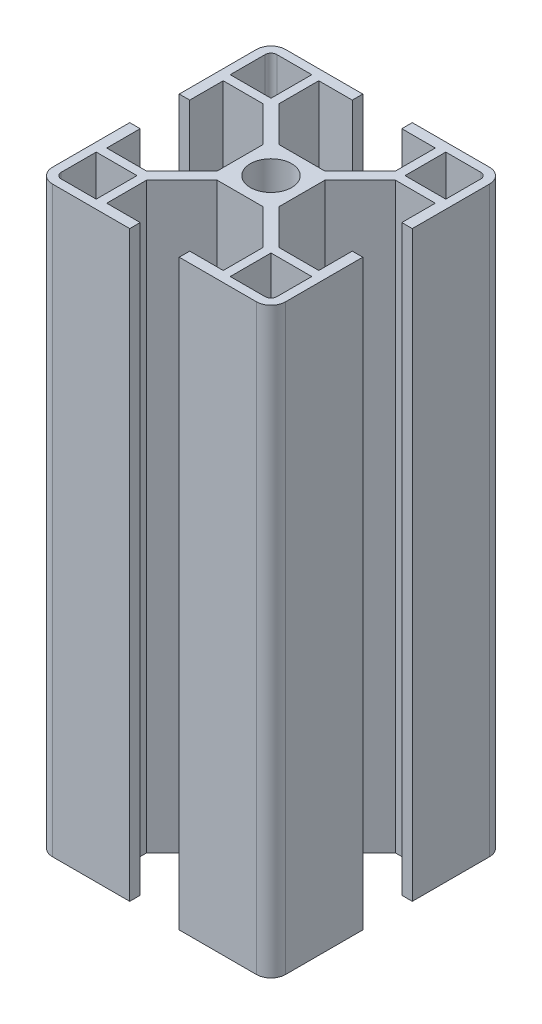
SolidWorks part; units mm, degrees
ref_plane "前视基准面" through (0, 0, 0) normal (0, 0, 1) x (1, 0, 0)
ref_plane "上视基准面" through (0, 0, 0) normal (0, 1, 0) x (1, 0, 0)
ref_plane "右视基准面" through (0, 0, 0) normal (1, 0, 0) x (0, 0, -1)
other "Configuration Table"
sketch "草图1" plane through (0, 0, 0) normal (0, 1, 0) x (1, 0, 0)
  line L0 (-28.4403, 0) -> (36.2792, 0) construction
  line L1 (0, 26.4889) -> (0, -19.5972) construction
  line L2 (0, 0) -> (-20.5491, 20.5491) construction
  line L3 (-20, 20) -> (-4.25, 20)
  line L4 (-4.25, 20) -> (-4.25, 18.2)
  line L5 (-4.25, 18.2) -> (-10, 18.2)
  line L6 (-10, 18.2) -> (-10, 11.3435)
  line L7 (-18.5, 18.5) -> (-11.5, 18.5)
  line L8 (-11.5, 18.5) -> (-11.5, 11.5)
  line L9 (-10, 11.3435) -> (-3.9565, 5.3)
  line L10 (-3.9565, 5.3) -> (3.9565, 5.3)
  line L11 (-5.3, 3.9565) -> (-5.3, -3.9565)
  line L12 (-11.3435, 10) -> (-5.3, 3.9565)
  line L13 (-18.5, 11.5) -> (-11.5, 11.5)
  line L14 (-18.5, 18.5) -> (-18.5, 11.5)
  line L15 (-18.2, 10) -> (-11.3435, 10)
  line L16 (-18.2, 4.25) -> (-18.2, 10)
  line L17 (-20, 4.25) -> (-18.2, 4.25)
  line L18 (-20, 20) -> (-20, 4.25)
  line L19 (20, 20) -> (20, 4.25)
  line L20 (20, 4.25) -> (18.2, 4.25)
  line L21 (18.2, 4.25) -> (18.2, 10)
  line L22 (18.2, 10) -> (11.3435, 10)
  line L23 (18.5, 18.5) -> (18.5, 11.5)
  line L24 (18.5, 11.5) -> (11.5, 11.5)
  line L25 (11.3435, 10) -> (5.3, 3.9565)
  line L26 (5.3, 3.9565) -> (5.3, -3.9565)
  line L27 (10, 11.3435) -> (3.9565, 5.3)
  line L28 (11.5, 18.5) -> (11.5, 11.5)
  line L29 (18.5, 18.5) -> (11.5, 18.5)
  line L30 (10, 18.2) -> (10, 11.3435)
  line L31 (4.25, 18.2) -> (10, 18.2)
  line L32 (4.25, 20) -> (4.25, 18.2)
  line L33 (20, 20) -> (4.25, 20)
  line L34 (0, -26.4889) -> (0, 19.5972) construction
  line L35 (20, -20) -> (4.25, -20)
  line L36 (4.25, -20) -> (4.25, -18.2)
  line L37 (4.25, -18.2) -> (10, -18.2)
  line L38 (10, -18.2) -> (10, -11.3435)
  line L39 (18.5, -18.5) -> (11.5, -18.5)
  line L40 (11.5, -18.5) -> (11.5, -11.5)
  line L41 (10, -11.3435) -> (3.9565, -5.3)
  line L42 (11.3435, -10) -> (5.3, -3.9565)
  line L43 (18.5, -11.5) -> (11.5, -11.5)
  line L44 (18.5, -18.5) -> (18.5, -11.5)
  line L45 (18.2, -10) -> (11.3435, -10)
  line L46 (18.2, -4.25) -> (18.2, -10)
  line L47 (20, -4.25) -> (18.2, -4.25)
  line L48 (20, -20) -> (20, -4.25)
  line L49 (-20, -20) -> (-20, -4.25)
  line L50 (-20, -4.25) -> (-18.2, -4.25)
  line L51 (-18.2, -4.25) -> (-18.2, -10)
  line L52 (-18.2, -10) -> (-11.3435, -10)
  line L53 (-18.5, -18.5) -> (-18.5, -11.5)
  line L54 (-18.5, -11.5) -> (-11.5, -11.5)
  line L55 (-11.3435, -10) -> (-5.3, -3.9565)
  line L56 (-3.9565, -5.3) -> (3.9565, -5.3)
  line L57 (-10, -11.3435) -> (-3.9565, -5.3)
  line L58 (-11.5, -18.5) -> (-11.5, -11.5)
  line L59 (-18.5, -18.5) -> (-11.5, -18.5)
  line L60 (-10, -18.2) -> (-10, -11.3435)
  line L61 (-4.25, -18.2) -> (-10, -18.2)
  line L62 (-4.25, -20) -> (-4.25, -18.2)
  line L63 (-20, -20) -> (-4.25, -20)
  circle A0 centre (0, 0) radius 3.55
  point P37 (0, 5.3)
  point P53 (5.3, 0)
  point P67 (-5.3, 0)
  point P73 (0, -5.3)
  point P74 (-67.2045, 32.6318)
  dimension "D9" = 3.55
  dimension "D1" = 20
  dimension "D3" = 1.5
  dimension "D4" = 1.8
  dimension "D5" = 4.25
  dimension "D6" = 1.9
  dimension "D7" = 10
  dimension "D8" = 5.3
  dimension "D10" = 1.5
extrude "凸台-拉伸1" add sketch "草图1" along normal blind 100
fillet "圆角1" radius 1 4 edges at (18.5, 50, -18.5) (-18.5, 50, -18.5) (-18.5, 50, 18.5) (18.5, 50, 18.5)
fillet "圆角2" radius 2.5 4 edges at (-20, 50, 20) (20, 50, 20) (20, 50, -20) (-20, 50, -20)
